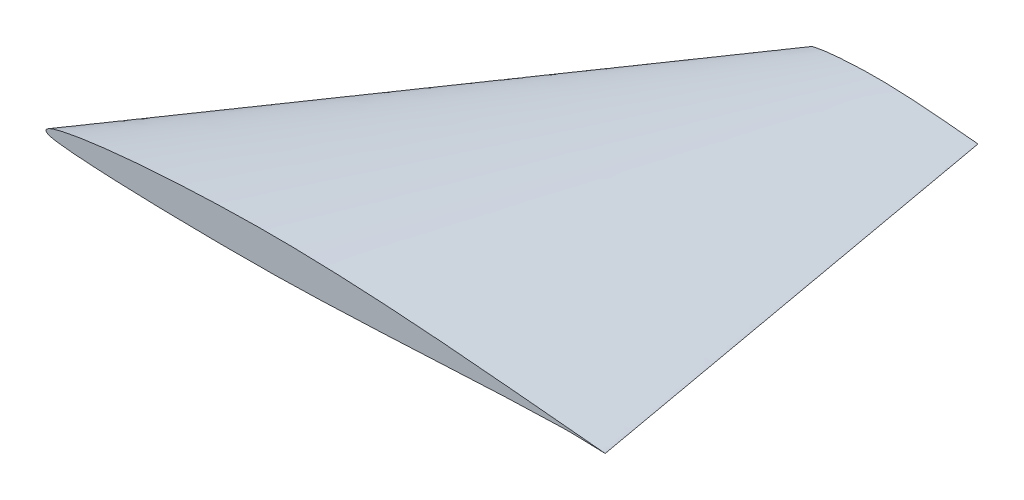
SolidWorks part; units mm, degrees
ref_plane "Front Plane" through (0, 0, 0) normal (0, 0, 1) x (1, 0, 0)
ref_plane "Top Plane" through (0, 0, 0) normal (0, 1, 0) x (1, 0, 0)
ref_plane "Right Plane" through (0, 0, 0) normal (1, 0, 0) x (0, 0, -1)
curve "Curve1"
  spline degree 3 poles (7512.399, 21.2388, 0) (8203.2595, -15.8322, 0) (7513.3519, 42.1095, 0) (7193.4422, 73.6677, 0) (6774.3282, 112.9533, 0) (6381.5746, 149.054, 0) (5981.5484, 184.4784, 0) (5583.1806, 216.6714, 0) (5184.1684, 246.1918, 0) (4785.1429, 271.9717, 0) (4385.9337, 293.3752, 0) (3986.629, 310.1867, 0) (3587.2208, 321.0495, 0) (3187.727, 325.8561, 0) (2788.2189, 320.6453, 0) (2388.7425, 310.365, 0) (1989.2714, 293.5394, 0) (1589.8955, 269.6706, 0) (1190.5368, 238.4305, 0) (858.0326, 204.0929, 0) (592.2576, 169.4022, 0) (392.7788, 138.4756, 0) (226.5583, 105.0644, 0) (114.5266, 76.5641, 0) (61.8453, 55.7367, 0) (27.0243, 39.6534, 0) (-21.8391, -1.9311, 0) (33.3183, -32.9811, 0) (69.4087, -43.6826, 0) (123.6037, -56.5529, 0) (236.6732, -71.2511, 0) (403.6595, -87.6019, 0) (603.2165, -101.4161, 0) (868.9173, -116.5412, 0) (1200.8474, -130.2234, 0) (1599.0388, -142.1668, 0) (1997.0767, -150.2218, 0) (2395.0045, -154.8728, 0) (2792.9004, -155.9632, 0) (3190.7985, -154.6067, 0) (3588.6964, -146.0223, 0) (3986.6382, -133.8676, 0) (4384.6438, -118.3503, 0) (4782.7662, -100.7211, 0) (5180.9825, -81.5014, 0) (5579.4516, -61.1987, 0) (5977.5847, -41.0889, 0) (6377.7846, -21.745, 0) (6771.0798, -3.9492, 0) (7191.075, 6.9211, 0) (7512.399, 21.2388, 0) (8203.2595, -15.8322, 0) (7513.3519, 42.1095, 0) knots -0.074766 -0.049849 -0.024927 0 0.024956 0.049905 0.07487 0.099834 0.124805 0.149776 0.174738 0.199694 0.224645 0.249586 0.27452 0.299451 0.324382 0.34932 0.374267 0.399237 0.424225 0.449262 0.461814 0.474399 0.487067 0.493487 0.496129 0.497491 0.501025 0.504502 0.505834 0.508423 0.514755 0.527287 0.539769 0.552224 0.577107 0.601969 0.626809 0.651646 0.676476 0.701307 0.726142 0.750988 0.775847 0.800716 0.8256 0.850496 0.875398 0.900311 0.925234 0.950151 0.975073 1 1.024956 1.049905 1.07487 periodic
sketch "Sketch2" plane through (0, 0, 0) normal (0, 0, 1) x (1, 0, 0)
  spline S0 degree 3 poles (7512.399, 21.2388) (8203.2595, -15.8322) (7513.3519, 42.1095) (7193.4422, 73.6677) (6774.3282, 112.9533) (6381.5746, 149.054) (5981.5484, 184.4784) (5583.1806, 216.6714) (5184.1684, 246.1918) (4785.1429, 271.9717) (4385.9337, 293.3752) (3986.629, 310.1867) (3587.2208, 321.0495) (3187.727, 325.8561) (2788.2189, 320.6453) (2388.7425, 310.365) (1989.2714, 293.5394) (1589.8955, 269.6706) (1190.5368, 238.4305) (858.0326, 204.0929) (592.2576, 169.4022) (392.7788, 138.4756) (226.5583, 105.0644) (114.5266, 76.5641) (61.8453, 55.7367) (27.0243, 39.6534) (-21.8391, -1.9311) (33.3183, -32.9811) (69.4087, -43.6826) (123.6037, -56.5529) (236.6732, -71.2511) (403.6595, -87.6019) (603.2165, -101.4161) (868.9173, -116.5412) (1200.8474, -130.2234) (1599.0388, -142.1668) (1997.0767, -150.2218) (2395.0045, -154.8728) (2792.9004, -155.9632) (3190.7985, -154.6067) (3588.6964, -146.0223) (3986.6382, -133.8676) (4384.6438, -118.3503) (4782.7662, -100.7211) (5180.9825, -81.5014) (5579.4516, -61.1987) (5977.5847, -41.0889) (6377.7846, -21.745) (6771.0798, -3.9492) (7191.075, 6.9211) (7512.399, 21.2388) (8203.2595, -15.8322) (7513.3519, 42.1095) knots -0.074766 -0.049849 -0.024927 0 0.024956 0.049905 0.07487 0.099834 0.124805 0.149776 0.174738 0.199694 0.224645 0.249586 0.27452 0.299451 0.324382 0.34932 0.374267 0.399237 0.424225 0.449262 0.461814 0.474399 0.487067 0.493487 0.496129 0.497491 0.501025 0.504502 0.505834 0.508423 0.514755 0.527287 0.539769 0.552224 0.577107 0.601969 0.626809 0.651646 0.676476 0.701307 0.726142 0.750988 0.775847 0.800716 0.8256 0.850496 0.875398 0.900311 0.925234 0.950151 0.975073 1 1.024956 1.049905 1.07487 only from (7973.1108, 0) to (7973.1108, 0) construction
  spline S1 degree 3 poles (7512.399, 21.2388) (8203.2595, -15.8322) (7513.3519, 42.1095) (7193.4422, 73.6677) (6774.3282, 112.9533) (6381.5746, 149.054) (5981.5484, 184.4784) (5583.1806, 216.6714) (5184.1684, 246.1918) (4785.1429, 271.9717) (4385.9337, 293.3752) (3986.629, 310.1867) (3587.2208, 321.0495) (3187.727, 325.8561) (2788.2189, 320.6453) (2388.7425, 310.365) (1989.2714, 293.5394) (1589.8955, 269.6706) (1190.5368, 238.4305) (858.0326, 204.0929) (592.2576, 169.4022) (392.7788, 138.4756) (226.5583, 105.0644) (114.5266, 76.5641) (61.8453, 55.7367) (27.0243, 39.6534) (-21.8391, -1.9311) (33.3183, -32.9811) (69.4087, -43.6826) (123.6037, -56.5529) (236.6732, -71.2511) (403.6595, -87.6019) (603.2165, -101.4161) (868.9173, -116.5412) (1200.8474, -130.2234) (1599.0388, -142.1668) (1997.0767, -150.2218) (2395.0045, -154.8728) (2792.9004, -155.9632) (3190.7985, -154.6067) (3588.6964, -146.0223) (3986.6382, -133.8676) (4384.6438, -118.3503) (4782.7662, -100.7211) (5180.9825, -81.5014) (5579.4516, -61.1987) (5977.5847, -41.0889) (6377.7846, -21.745) (6771.0798, -3.9492) (7191.075, 6.9211) (7512.399, 21.2388) (8203.2595, -15.8322) (7513.3519, 42.1095) knots -0.074766 -0.049849 -0.024927 0 0.024956 0.049905 0.07487 0.099834 0.124805 0.149776 0.174738 0.199694 0.224645 0.249586 0.27452 0.299451 0.324382 0.34932 0.374267 0.399237 0.424225 0.449262 0.461814 0.474399 0.487067 0.493487 0.496129 0.497491 0.501025 0.504502 0.505834 0.508423 0.514755 0.527287 0.539769 0.552224 0.577107 0.601969 0.626809 0.651646 0.676476 0.701307 0.726142 0.750988 0.775847 0.800716 0.8256 0.850496 0.875398 0.900311 0.925234 0.950151 0.975073 1 1.024956 1.049905 1.07487 only from (7973.1108, 0) to (7973.1108, 0)
ref_plane "Plane1" through (0, 0, -6480.4442) normal (0, 0, 1) x (1, 0, 0)
curve "Curve2"
  spline degree 3 poles (6670.6549, 6.372, 6480.4442) (6877.925, -4.7499, 6480.4442) (6670.9408, 12.6336, 6480.4442) (6574.9624, 22.1016, 6480.4442) (6449.221, 33.8879, 6480.4442) (6331.3881, 44.7188, 6480.4442) (6211.3734, 55.3467, 6480.4442) (6091.8562, 65.0052, 6480.4442) (5972.1457, 73.8618, 6480.4442) (5852.4312, 81.5962, 6480.4442) (5732.6616, 88.0176, 6480.4442) (5612.8633, 93.0613, 6480.4442) (5493.0339, 96.3204, 6480.4442) (5373.1789, 97.7624, 6480.4442) (5253.3196, 96.1991, 6480.4442) (5133.4699, 93.1148, 6480.4442) (5013.6216, 88.0669, 6480.4442) (4893.802, 80.9058, 6480.4442) (4773.9875, 71.5333, 6480.4442) (4674.2305, 61.2314, 6480.4442) (4594.4935, 50.8236, 6480.4442) (4534.6464, 41.545, 6480.4442) (4484.7774, 31.5211, 6480.4442) (4451.1659, 22.9705, 6480.4442) (4435.3606, 16.722, 6480.4442) (4424.9138, 11.8967, 6480.4442) (4410.2539, -0.5794, 6480.4442) (4426.8021, -9.8949, 6480.4442) (4437.6298, -13.1055, 6480.4442) (4453.8893, -16.9668, 6480.4442) (4487.812, -21.3766, 6480.4442) (4537.9108, -26.2821, 6480.4442) (4597.7813, -30.4266, 6480.4442) (4677.4962, -34.9644, 6480.4442) (4777.0809, -39.0693, 6480.4442) (4896.5452, -42.6525, 6480.4442) (5015.9634, -45.0691, 6480.4442) (5135.3486, -46.4645, 6480.4442) (5254.7242, -46.7916, 6480.4442) (5374.1004, -46.3847, 6480.4442) (5493.4767, -43.8092, 6480.4442) (5612.866, -40.1626, 6480.4442) (5732.2746, -35.5071, 6480.4442) (5851.7182, -30.2181, 6480.4442) (5971.1899, -24.4518, 6480.4442) (6090.7375, -18.3607, 6480.4442) (6210.1843, -12.3274, 6480.4442) (6330.2511, -6.5239, 6480.4442) (6448.2464, -1.1848, 6480.4442) (6574.2522, 2.0764, 6480.4442) (6670.6549, 6.372, 6480.4442) (6877.925, -4.7499, 6480.4442) (6670.9408, 12.6336, 6480.4442) knots -0.074766 -0.049849 -0.024927 0 0.024956 0.049905 0.07487 0.099834 0.124805 0.149776 0.174738 0.199694 0.224645 0.249586 0.27452 0.299451 0.324382 0.34932 0.374267 0.399237 0.424225 0.449262 0.461814 0.474399 0.487067 0.493487 0.496129 0.497491 0.501025 0.504502 0.505834 0.508423 0.514755 0.527287 0.539769 0.552224 0.577107 0.601969 0.626809 0.651646 0.676476 0.701307 0.726142 0.750988 0.775847 0.800716 0.8256 0.850496 0.875398 0.900312 0.925234 0.950151 0.975073 1 1.024956 1.049905 1.07487 periodic
sketch "Sketch3" plane through (0, 0, -6480.4442) normal (0, 0, 1) x (1, 0, 0)
  spline S0 degree 3 poles (6670.6549, 6.372) (6877.925, -4.7499) (6670.9408, 12.6336) (6574.9624, 22.1016) (6449.221, 33.8879) (6331.3881, 44.7188) (6211.3734, 55.3467) (6091.8562, 65.0052) (5972.1457, 73.8618) (5852.4312, 81.5962) (5732.6616, 88.0176) (5612.8633, 93.0613) (5493.0339, 96.3204) (5373.1789, 97.7624) (5253.3196, 96.1991) (5133.4699, 93.1148) (5013.6216, 88.0669) (4893.802, 80.9058) (4773.9875, 71.5333) (4674.2305, 61.2314) (4594.4935, 50.8236) (4534.6464, 41.545) (4484.7774, 31.5211) (4451.1659, 22.9705) (4435.3606, 16.722) (4424.9138, 11.8967) (4410.2539, -0.5794) (4426.8021, -9.8949) (4437.6298, -13.1055) (4453.8893, -16.9668) (4487.812, -21.3766) (4537.9108, -26.2821) (4597.7813, -30.4266) (4677.4962, -34.9644) (4777.0809, -39.0693) (4896.5452, -42.6525) (5015.9634, -45.0691) (5135.3486, -46.4645) (5254.7242, -46.7916) (5374.1004, -46.3847) (5493.4767, -43.8092) (5612.866, -40.1626) (5732.2746, -35.5071) (5851.7182, -30.2181) (5971.1899, -24.4518) (6090.7375, -18.3607) (6210.1843, -12.3274) (6330.2511, -6.5239) (6448.2464, -1.1848) (6574.2522, 2.0764) (6670.6549, 6.372) (6877.925, -4.7499) (6670.9408, 12.6336) knots -0.074766 -0.049849 -0.024927 0 0.024956 0.049905 0.07487 0.099834 0.124805 0.149776 0.174738 0.199694 0.224645 0.249586 0.27452 0.299451 0.324382 0.34932 0.374267 0.399237 0.424225 0.449262 0.461814 0.474399 0.487067 0.493487 0.496129 0.497491 0.501025 0.504502 0.505834 0.508423 0.514755 0.527287 0.539769 0.552224 0.577107 0.601969 0.626809 0.651646 0.676476 0.701307 0.726142 0.750988 0.775847 0.800716 0.8256 0.850496 0.875398 0.900312 0.925234 0.950151 0.975073 1 1.024956 1.049905 1.07487 only from (6808.8764, 0) to (6808.8764, 0) construction
  spline S1 degree 3 poles (6670.6549, 6.372) (6877.925, -4.7499) (6670.9408, 12.6336) (6574.9624, 22.1016) (6449.221, 33.8879) (6331.3881, 44.7188) (6211.3734, 55.3467) (6091.8562, 65.0052) (5972.1457, 73.8618) (5852.4312, 81.5962) (5732.6616, 88.0176) (5612.8633, 93.0613) (5493.0339, 96.3204) (5373.1789, 97.7624) (5253.3196, 96.1991) (5133.4699, 93.1148) (5013.6216, 88.0669) (4893.802, 80.9058) (4773.9875, 71.5333) (4674.2305, 61.2314) (4594.4935, 50.8236) (4534.6464, 41.545) (4484.7774, 31.5211) (4451.1659, 22.9705) (4435.3606, 16.722) (4424.9138, 11.8967) (4410.2539, -0.5794) (4426.8021, -9.8949) (4437.6298, -13.1055) (4453.8893, -16.9668) (4487.812, -21.3766) (4537.9108, -26.2821) (4597.7813, -30.4266) (4677.4962, -34.9644) (4777.0809, -39.0693) (4896.5452, -42.6525) (5015.9634, -45.0691) (5135.3486, -46.4645) (5254.7242, -46.7916) (5374.1004, -46.3847) (5493.4767, -43.8092) (5612.866, -40.1626) (5732.2746, -35.5071) (5851.7182, -30.2181) (5971.1899, -24.4518) (6090.7375, -18.3607) (6210.1843, -12.3274) (6330.2511, -6.5239) (6448.2464, -1.1848) (6574.2522, 2.0764) (6670.6549, 6.372) (6877.925, -4.7499) (6670.9408, 12.6336) knots -0.074766 -0.049849 -0.024927 0 0.024956 0.049905 0.07487 0.099834 0.124805 0.149776 0.174738 0.199694 0.224645 0.249586 0.27452 0.299451 0.324382 0.34932 0.374267 0.399237 0.424225 0.449262 0.461814 0.474399 0.487067 0.493487 0.496129 0.497491 0.501025 0.504502 0.505834 0.508423 0.514755 0.527287 0.539769 0.552224 0.577107 0.601969 0.626809 0.651646 0.676476 0.701307 0.726142 0.750988 0.775847 0.800716 0.8256 0.850496 0.875398 0.900312 0.925234 0.950151 0.975073 1 1.024956 1.049905 1.07487 only from (6808.8764, 0) to (6808.8764, 0)
loft "Loft1" add profiles "Sketch3", "Sketch2" connector at (4420.1738, 7.0713, -6480.4442) connector at (7.9303, 19.8224, 0)
